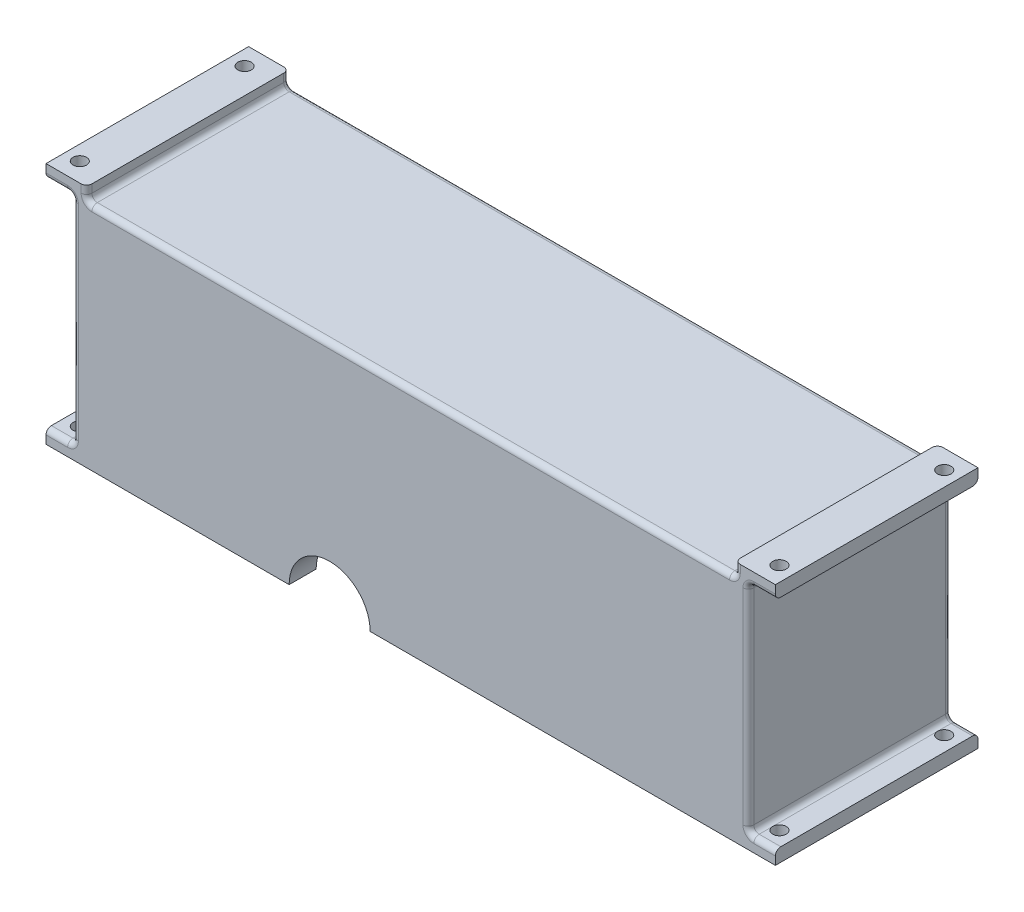
SolidWorks part; units mm, degrees
ref_plane "Front Plane" through (0, 0, 0) normal (0, 0, 1) x (1, 0, 0)
ref_plane "Top Plane" through (0, 0, 0) normal (0, 1, 0) x (1, 0, 0)
ref_plane "Right Plane" through (0, 0, 0) normal (1, 0, 0) x (0, 0, -1)
sketch "Sketch1" plane through (0, 0, 0) normal (0, 1, 0) x (1, 0, 0)
  line L0 (-125, 37.5) -> (125, -37.5) construction
  line L1 (-125, -37.5) -> (125, -37.5)
  line L2 (-125, -37.5) -> (-125, 37.5)
  line L3 (-125, 37.5) -> (125, 37.5)
  line L4 (125, -37.5) -> (125, 37.5)
  dimension "D1" = 75
  dimension "D2" = 250
extrude "Boss-Extrude1" add sketch "Sketch1" along normal blind 85
shell "Shell1" thickness 10 removed face at (0, 0, 0)
sketch "Sketch2" plane through (0, 0, 0) normal (0, -1, 0) x (-1, 0, 0)
  line L0 (-115, -27.5) -> (-115, 27.5) construction
  line L3 (-115, -7.5) -> (115, -7.5)
  line L4 (-115, -7.5) -> (-115, 7.5)
  line L5 (-115, 7.5) -> (115, 7.5)
  line L6 (115, -7.5) -> (115, 7.5)
  line L7 (115, 27.5) -> (115, -27.5) construction
  line L8 (-115, 7.5) -> (115, -7.5) construction
  dimension "D1" = 15
extrude "Boss-Extrude2" add sketch "Sketch2" against normal up to surface (75 mm away) up to face at (0, 75, 0)
sketch "Sketch3" plane through (0, 85, 0) normal (0, 1, 0) x (1, 0, 0)
  line L9 (-120, 37.5) -> (-135, 37.5)
  line L10 (-120, 37.5) -> (-120, -37.5)
  line L11 (-120, -37.5) -> (-135, -37.5)
  line L12 (-135, 37.5) -> (-135, -37.5)
  line L13 (0, 37.5) -> (0, -37.5) construction
  line L14 (120, -37.5) -> (135, -37.5)
  line L15 (120, 37.5) -> (120, -37.5)
  line L16 (120, 37.5) -> (135, 37.5)
  line L17 (135, 37.5) -> (135, -37.5)
  line L18 (-125, -37.5) -> (125, -37.5) construction
  line L19 (125, 37.5) -> (-125, 37.5) construction
  line L21 (-125, 37.5) -> (-125, -37.5) construction
  circle A0 centre (-129.5, 30.5) radius 2.5
  circle A1 centre (-129.5, -30.5) radius 2.5
  circle A2 centre (129.5, -30.5) radius 2.5
  circle A3 centre (129.5, 30.5) radius 2.5
  dimension "D1" = 5
  dimension "D2" = 15
  dimension "D3" = 7
  dimension "D4" = 7
  dimension "D5" = 5
  dimension "D6" = 5.5
extrude "Boss-Extrude3" add sketch "Sketch3" along normal blind 5
sketch "Sketch5" plane through (0, 0, 0) normal (0, 0, 1) x (1, 0, 0)
  line L0 (125, 0) -> (-125, 0) construction
  line L1 (-125, 0) -> (125, 0) construction
  circle A0 centre (-30, 0) radius 72
  circle A1 centre (54, 0) radius 12
  circle A2 centre (-30, 0) radius 15
  circle A3 centre (54, 0) radius 48
  circle A4 centre (-18, 0) radius 24
  circle A5 centre (-54, 0) radius 12
  circle A6 centre (-54, 0) radius 3.75
  circle A7 centre (54, 0) radius 5
  circle A8 centre (-18, 0) radius 5
  point P18 (190.3823, 0)
  dimension "D1" = 144
  dimension "D3" = 24
  dimension "D4" = 30
  dimension "D5" = 96
  dimension "D6" = 48
  dimension "D7" = 24
  dimension "D8" = 7.5
  dimension "D9" = 10
  dimension "D10" = 10
  dimension "D2" = 85
fillet "Fillet2" radius 2 2 edges at (120, 85, 0) (-120, 85, 0)
sketch "Sketch6" plane through (0, 0, 0) normal (0, -1, 0) x (1, 0, 0)
  line L1 (-125, -37.5) -> (-135, -37.5)
  line L2 (-125, -37.5) -> (-125, 37.5)
  line L3 (-125, 37.5) -> (-135, 37.5)
  line L4 (-135, -37.5) -> (-135, 37.5)
  line L7 (0, 37.5) -> (0, -37.5) construction
  line L8 (125, -37.5) -> (-125, -37.5) construction
  line L9 (-125, 37.5) -> (125, 37.5) construction
  line L10 (125, 37.5) -> (135, 37.5)
  line L11 (125, -37.5) -> (135, -37.5)
  line L12 (125, -37.5) -> (125, 37.5)
  line L13 (135, -37.5) -> (135, 37.5)
  circle A0 centre (-129.5, 30.5) radius 2.5
  circle A1 centre (-129.5, -30.5) radius 2.5
  circle A2 centre (129.5, -30.5) radius 2.5
  circle A3 centre (129.5, 30.5) radius 2.5
  dimension "D2" = 5
  dimension "D3" = 5
  dimension "D1" = 10
extrude "Boss-Extrude5" add sketch "Sketch6" against normal blind 5
fillet "Fillet3" radius 2 8 edges at (-130, 85, -37.5) (-130, 85, 37.5) (-125, 45, -37.5) (-125, 85, 0) (-125, 45, 37.5) (-130, 5, -37.5) (-130, 5, 37.5) (-125, 5, 0)
fillet "Fillet4" radius 2 8 edges at (130, 85, 37.5) (130, 85, -37.5) (125, 45, 37.5) (125, 85, 0) (125, 45, -37.5) (130, 5, -37.5) (130, 5, 37.5) (125, 5, 0)
fillet "Fillet5" radius 2 10 edges at (120, 88.5, -37.5) (119.4142, 85.5858, -37.5) (-120, 88.5, -37.5) (-119.4142, 85.5858, -37.5) (-120, 88.5, 37.5) (-119.4142, 85.5858, 37.5) (120, 88.5, 37.5) (119.4142, 85.5858, 37.5) (0, 85, -37.5) (0, 85, 37.5)
extrude "Cut-Extrude1" cut sketch "Sketch5" against normal offset from surface (35 mm away) 10 from surface contours A8 A2 A4 | A5 A2 A4 | A5 A2 | A5 A4 A2 | A2 A8 region at (-41.6597, 7.1083, 0) region at (-30.1159, 0, 0) region at (-41.6597, -7.1083, 0) region at (-18.7215, 0, 0) region at (-43.5343, 0, 0) up to face at (0, 37.5, -7.5) starting at face at (0, 56.2883, 37.5)
extrude "Cut-Extrude2" cut sketch "Sketch5<16>" against normal mid plane 65 contours A7
sketch "Sketch5<16>" plane through (0, 0, 0) normal (0, 0, 1) x (1, 0, 0) same geometry as "Sketch5"
extrude "Cut-Extrude3" cut sketch "Sketch5<17>" along normal offset from surface (35 mm away) 10 from surface contours A6 up to face at (6, 21.25, 7.5) starting at face at (0, 56.2883, -37.5)
sketch "Sketch5<17>" plane through (0, 0, 0) normal (0, 0, 1) x (1, 0, 0) same geometry as "Sketch5"
extrude "Cut-Extrude4" cut sketch "Sketch5<18>" along normal offset from surface (25 mm away) 10 from surface contours A8 up to face at (6, 21.25, 7.5) starting at face at (0, 19.8438, -27.5)
sketch "Sketch5<18>" plane through (0, 0, 0) normal (0, 0, 1) x (1, 0, 0) same geometry as "Sketch5"
extrude "Cut-Extrude5" cut sketch "Sketch5<19>" against normal offset from surface (25 mm away) 5 from surface contours A8 up to face at (-4.5, 51.7539, -37.5) starting at face at (-3.6, 16.375, -7.5)
sketch "Sketch5<19>" plane through (0, 0, 0) normal (0, 0, 1) x (1, 0, 0) same geometry as "Sketch5"
